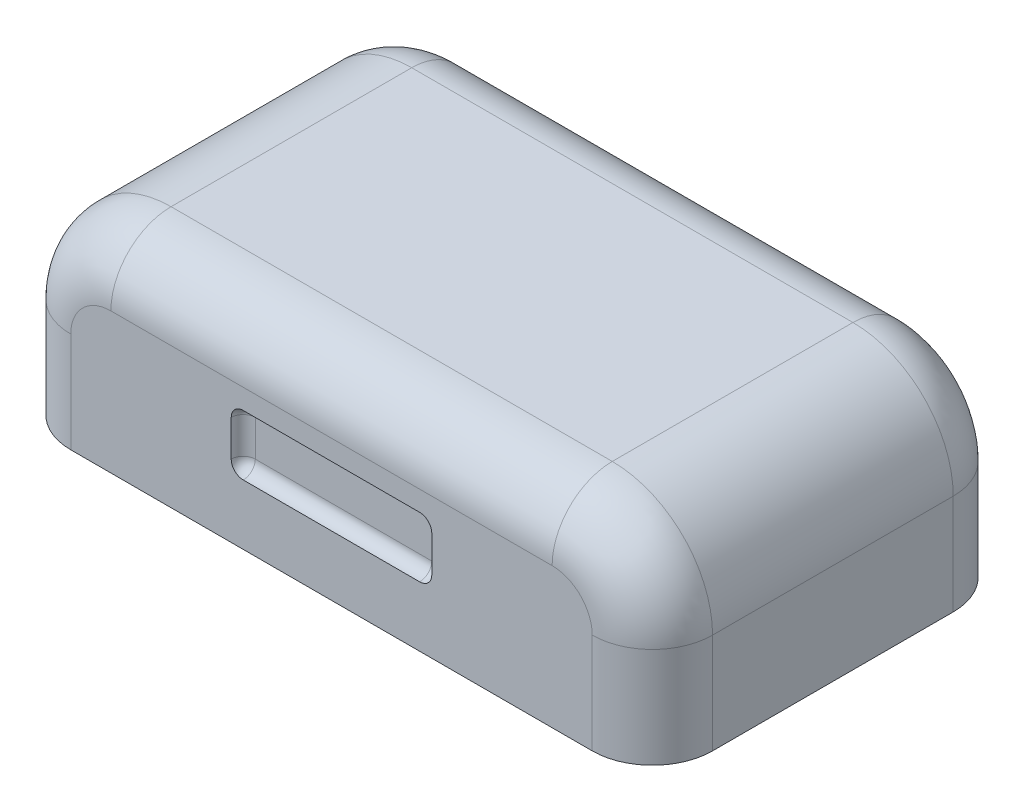
SolidWorks part; units mm, degrees
ref_plane "Plan de face" through (0, 0, 0) normal (0, 0, 1) x (1, 0, 0)
ref_plane "Plan de dessus" through (0, 0, 0) normal (0, 1, 0) x (1, 0, 0)
ref_plane "Plan de droite" through (0, 0, 0) normal (1, 0, 0) x (0, 0, -1)
sketch "Esquisse1" plane through (0, 0, 0) normal (0, 1, 0) x (1, 0, 0)
  line L1 (-44.6588, 68.7058) -> (115.3412, 68.7058)
  line L2 (-44.6588, 68.7058) -> (-44.6588, -21.2942)
  line L3 (-44.6588, -21.2942) -> (115.3412, -21.2942)
  line L4 (115.3412, 68.7058) -> (115.3412, -21.2942)
  dimension "D1" = 90
  dimension "D2" = 160
extrude "Extrusion1" add sketch "Esquisse1" along normal blind 50
fillet "Congé1" radius 25 2 edges at (-44.6588, 50, -23.7058) (115.3412, 50, -23.7058)
fillet "Congé2" radius 15 10 edges at (115.3412, 12.5, 21.2942) (108.0189, 42.6777, 21.2942) (35.3412, 50, 21.2942) (-37.3364, 42.6777, 21.2942) (-44.6588, 12.5, -68.7058) (-37.3364, 42.6777, -68.7058) (35.3412, 50, -68.7058) (108.0189, 42.6777, -68.7058) (-44.6588, 12.5, 21.2942) (115.3412, 12.5, -68.7058)
shell "Coque1" thickness 4 removed face at (35.3412, 0, -23.7058)
sketch "Esquisse2" plane through (0, 0, 21.2942) normal (0, 0, 1) x (1, 0, 0)
  line L0 (-29.6588, 0) -> (100.3412, 0) construction
  line L1 (10.3412, 30) -> (60.3412, 30)
  line L2 (10.3412, 30) -> (10.3412, 15)
  line L3 (10.3412, 15) -> (60.3412, 15)
  line L4 (60.3412, 30) -> (60.3412, 15)
  line L6 (35.3412, 0) -> (35.3412, 35) construction
  line L7 (90.3412, 35) -> (-19.6588, 35) construction
  dimension "D1" = 50
  dimension "D2" = 15
  dimension "D3" = 15
  dimension "D4" = 25
extrude "Enlèv. mat.-Extru.1" cut sketch "Esquisse2" against normal blind 3
fillet "Congé4" radius 3 1 edges at (35.3412, 15, 18.2942) type face fillet first side face at (35.3412, 15, 19.7942) second side face at (35.3412, 22.5, 18.2942)
fillet "Congé5" radius 3 1 edges at (35.3412, 30, 18.2942) type face fillet first side face at (35.3412, 30, 19.7942) second side face at (35.3412, 24, 18.2942)
fillet "Congé6" radius 3 1 edges at (10.3412, 22.5, 18.2942) type face fillet first side face at (10.3412, 22.5, 19.4836) second side face at (35.3412, 22.5, 18.2942)
fillet "Congé7" radius 3 1 edges at (60.3412, 22.5, 18.2942) type face fillet first side face at (60.3412, 22.5, 19.4836) second side face at (36.8412, 22.5, 18.2942)
ref_plane "Plan1" through (0, 0, -23.7058) normal (0, 0, 1) x (1, 0, 0)
mirror "Symétrie1" about plane through (0, 0, -23.7058) normal (0, 0, 1) of "Congé7", "Congé6", "Congé5", "Congé4", "Enlèv. mat.-Extru.1"
scale "Echelle1" [suppressed]
